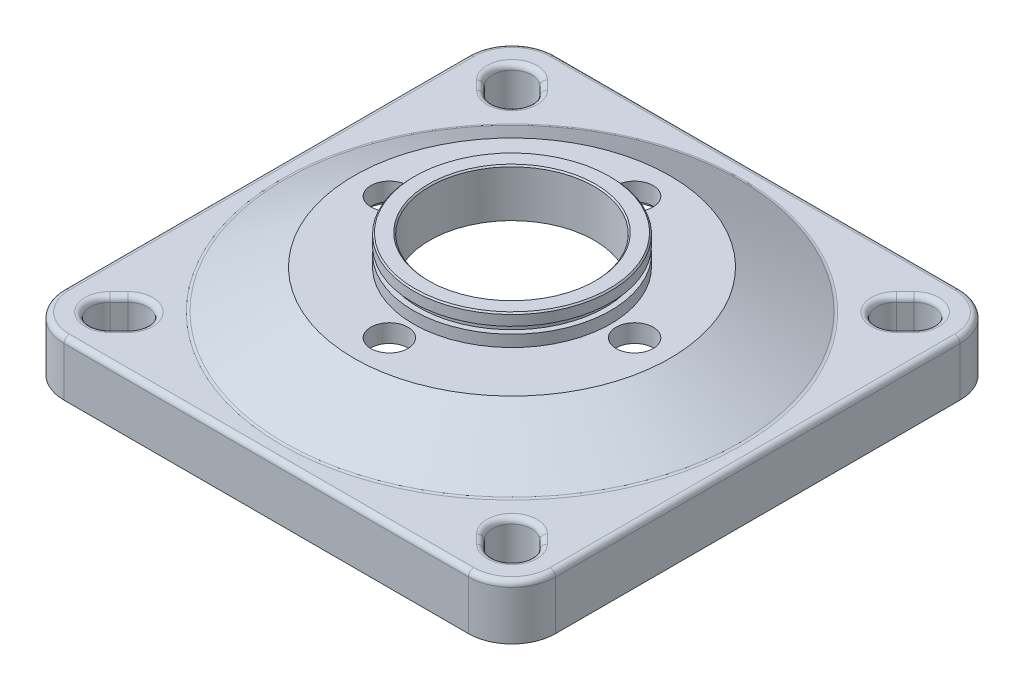
SolidWorks part; units mm, degrees
ref_plane "Front Plane" through (0, 0, 0) normal (0, 0, 1) x (1, 0, 0)
ref_plane "Top Plane" through (0, 0, 0) normal (0, 1, 0) x (1, 0, 0)
ref_plane "Right Plane" through (0, 0, 0) normal (1, 0, 0) x (0, 0, -1)
sketch "Sketch1" plane through (0, 0, 0) normal (0, 0, 1) x (1, 0, 0)
  line L0 (41.9647, 0) -> (-41.9647, 0) construction
  line L1 (-42, 0) -> (-42, 2.8529)
  line L2 (-42, 2.8529) -> (-29, 10)
  line L3 (-29, 10) -> (-18.1, 10)
  line L4 (-18.1, 10) -> (-18.1, 12.125)
  line L5 (-18.1, 12.125) -> (-17.1, 12.125)
  line L6 (-17.1, 12.125) -> (-17.1, 13.375)
  line L7 (-17.1, 13.375) -> (-18.1, 13.375)
  line L8 (-18.1, 13.375) -> (-18.1, 15.5)
  line L9 (-18.1, 15.5) -> (-15.1, 15.5)
  line L10 (-20.1376, 12.75) -> (-11.0446, 12.75) construction
  line L11 (0, 0) -> (0, 22.8552) construction
  line L12 (-15.1, 15.5) -> (-15.1, 7.5)
  line L13 (-15.1, 7.5) -> (-28.3581, 7.5)
  line L14 (-28.3581, 7.5) -> (-42, 0)
  point P4 (0, 0)
  dimension "D1" = 5.5
  dimension "D2" = 1.25
  dimension "D3" = 3
  dimension "D4" = 1
  dimension "D5" = 15.1
  dimension "D6" = 29
  dimension "D7" = 42
  dimension "D8" = 10
  dimension "D9" = 2.5
  dimension "D10" = 2.5
revolve "Revolve1" add sketch "Sketch1" angle 360 about L11
ref_plane "Plane1" through (0, 2.8529, 0) normal (0, 1, 0) x (1, 0, 0)
sketch "Sketch2" plane through (0, 2.8529, 0) normal (0, 1, 0) x (1, 0, 0)
  line L0 (36.0616, 36.0616) -> (32.7028, 32.7028)
  line L1 (37.1, -45.1) -> (-37.1, -45.1)
  line L2 (45.1, -37.1) -> (45.1, 37.1)
  line L3 (37.1, 45.1) -> (-37.1, 45.1)
  line L4 (-45.1, -37.1) -> (-45.1, 37.1)
  line L5 (45.1, -45.1) -> (-45.1, 45.1) construction
  line L6 (45.1, 45.1) -> (-45.1, -45.1) construction
  line L7 (36.0616, 36.0616) -> (39.4203, 39.4203)
  line L8 (34.3291, 39.4203) -> (32.7028, 37.794)
  line L9 (39.4203, 34.3291) -> (37.794, 32.7028)
  line L10 (34.3292, -39.4174) -> (32.7029, -37.791)
  line L11 (39.4204, -34.3262) -> (37.7941, -32.6999)
  line L12 (-39.4173, -34.3263) -> (-37.7909, -32.7)
  line L13 (-34.3261, -39.4175) -> (-32.6998, -37.7911)
  line L14 (-34.3262, 39.4202) -> (-32.6999, 37.7939)
  line L15 (-39.4174, 34.329) -> (-37.791, 32.7027)
  arc A0 (39.4203, 34.3291) -> (34.3291, 39.4203) centre (36.8747, 36.8747) ccw
  arc A1 (32.7028, 37.794) -> (37.794, 32.7028) centre (35.2484, 35.2484) ccw
  circle A2 centre (0, 0) radius 50.9987 construction
  arc A3 (45.1, -37.1) -> (37.1, -45.1) centre (37.1, -37.1) cw
  arc A4 (-37.1, -45.1) -> (-45.1, -37.1) centre (-37.1, -37.1) cw
  arc A5 (-45.1, 37.1) -> (-37.1, 45.1) centre (-37.1, 37.1) cw
  arc A6 (45.1, 37.1) -> (37.1, 45.1) centre (37.1, 37.1) ccw
  arc A7 (34.3292, -39.4174) -> (39.4204, -34.3262) centre (36.8748, -36.8718) ccw
  arc A8 (37.7941, -32.6999) -> (32.7029, -37.791) centre (35.2485, -35.2455) ccw
  arc A9 (-39.4173, -34.3263) -> (-34.3261, -39.4175) centre (-36.8717, -36.8719) ccw
  arc A10 (-32.6998, -37.7911) -> (-37.7909, -32.7) centre (-35.2454, -35.2456) ccw
  arc A11 (-34.3262, 39.4202) -> (-39.4174, 34.329) centre (-36.8718, 36.8746) ccw
  arc A12 (-37.791, 32.7027) -> (-32.6999, 37.7939) centre (-35.2455, 35.2483) ccw
  circle A13 centre (0, 0) radius 42 construction
  circle A14 centre (0, 0) radius 42
  point P0 (0, 0)
  point P50 (0.0015, 0.0014)
  dimension "D3" = 7.2
  dimension "D4" = 4.75
  dimension "D6" = 8
  dimension "D1" = 90.2
  dimension "D2" = 90.2
  dimension "D5" = 4.75
  dimension "D7" = 4
extrude "Boss-Extrude1" add sketch "Sketch2" against normal blind 10 contours L2 A6 L3 A5 L4 A4 L1 A3 A12 L15 A11 L14 A10 L13 A9 L12 A8 L11 A7 L10 A1 L8 A0 L9 region at (0, 2.8529, 43.8244)
sketch "Sketch3" plane through (0, -7.1471, 0) normal (0, -1, 0) x (1, 0, 0)
  line L0 (-40.8304, 31.2137) -> (-40.0576, 30.4409)
  line L1 (-30.4409, 40.0576) -> (-31.215, 40.8316)
  line L4 (31.2137, 40.8304) -> (30.4409, 40.0576)
  line L5 (40.0576, 30.4409) -> (40.8316, 31.215)
  line L6 (-45.1, 37.1) -> (-45.1, -37.1) construction
  line L7 (37.1, 45.1) -> (-37.1, 45.1) construction
  line L10 (37.1, 45.1) -> (-37.1, 45.1)
  line L11 (-45.1, 37.1) -> (-45.1, 2.9917)
  line L12 (41.6852, 30.8619) -> (41.6975, 18.8382)
  line L13 (30.8602, 41.6839) -> (18.8672, 41.6839)
  line L14 (-30.8619, 41.6852) -> (-18.8382, 41.6975)
  line L15 (40.8304, -31.2137) -> (40.0576, -30.4409)
  line L16 (-41.6839, 30.8602) -> (-41.6839, 18.8672)
  line L17 (30.4409, -40.0576) -> (31.215, -40.8316)
  line L18 (-45.1, -2.9917) -> (-45.1, -37.1)
  line L19 (30.8619, -41.6852) -> (18.8382, -41.6975)
  line L20 (41.6839, -30.8602) -> (41.6839, -18.8672)
  line L21 (-31.2137, -40.8304) -> (-30.4409, -40.0576)
  line L22 (-40.0576, -30.4409) -> (-40.8316, -31.215)
  line L23 (-41.6852, -30.8619) -> (-41.6975, -18.8382)
  line L24 (-30.8602, -41.6839) -> (-18.8672, -41.6839)
  arc A1 (-18.6297, 40.7428) -> (-18.8382, 41.6975) centre (-18.8377, 41.1975) ccw
  arc A2 (-40.0576, 30.4409) -> (-35.6149, 28.4591) centre (-35.2493, 35.2493) ccw
  arc A4 (-27.6512, 35.2484) -> (-28.4591, 35.6149) centre (-27.9598, 35.6418) cw
  arc A9 (-35.2484, 27.6512) -> (-40.7294, 18.659) centre (0, 0) ccw
  arc A10 (-28.4591, 35.6149) -> (-30.4409, 40.0576) centre (-35.2493, 35.2493) ccw
  arc A11 (-18.6297, 40.7428) -> (-27.6512, 35.2484) centre (0, 0) ccw
  arc A12 (-31.215, 40.8316) -> (-30.8619, 41.6852) centre (-30.8614, 41.1852) cw
  arc A13 (-41.6839, 18.8672) -> (-40.7294, 18.659) centre (-41.1839, 18.8672) ccw
  arc A14 (-35.2484, 27.6512) -> (-35.6149, 28.4591) centre (-35.6418, 27.9598) ccw
  arc A15 (-41.6839, 30.8602) -> (-40.8304, 31.2137) centre (-41.1839, 30.8602) cw
  arc A16 (40.7428, 18.6297) -> (41.6975, 18.8382) centre (41.1975, 18.8377) ccw
  arc A17 (30.4409, 40.0576) -> (28.4591, 35.6149) centre (35.2493, 35.2493) ccw
  arc A18 (35.2484, 27.6512) -> (35.6149, 28.4591) centre (35.6418, 27.9598) cw
  arc A19 (32.7037, 37.7949) -> (37.7949, 32.7037) centre (35.2493, 35.2493) ccw
  arc A21 (27.6512, 35.2484) -> (18.659, 40.7294) centre (0, 0) ccw
  arc A22 (35.6149, 28.4591) -> (40.0576, 30.4409) centre (35.2493, 35.2493) ccw
  arc A23 (40.7428, 18.6297) -> (35.2484, 27.6512) centre (0, 0) ccw
  arc A24 (40.8316, 31.215) -> (41.6852, 30.8619) centre (41.1852, 30.8614) cw
  arc A25 (18.8672, 41.6839) -> (18.659, 40.7294) centre (18.8672, 41.1839) ccw
  arc A26 (27.6512, 35.2484) -> (28.4591, 35.6149) centre (27.9598, 35.6418) ccw
  arc A27 (30.8602, 41.6839) -> (31.2137, 40.8304) centre (30.8602, 41.1839) cw
  arc A28 (18.6297, -40.7428) -> (18.8382, -41.6975) centre (18.8377, -41.1975) ccw
  arc A29 (40.0576, -30.4409) -> (35.6149, -28.4591) centre (35.2493, -35.2493) ccw
  arc A30 (27.6512, -35.2484) -> (28.4591, -35.6149) centre (27.9598, -35.6418) cw
  arc A33 (35.2484, -27.6512) -> (40.7294, -18.659) centre (0, 0) ccw
  arc A34 (28.4591, -35.6149) -> (30.4409, -40.0576) centre (35.2493, -35.2493) ccw
  arc A35 (18.6297, -40.7428) -> (27.6512, -35.2484) centre (0, 0) ccw
  arc A36 (31.215, -40.8316) -> (30.8619, -41.6852) centre (30.8614, -41.1852) cw
  arc A37 (41.6839, -18.8672) -> (40.7294, -18.659) centre (41.1839, -18.8672) ccw
  arc A38 (35.2484, -27.6512) -> (35.6149, -28.4591) centre (35.6418, -27.9598) ccw
  arc A39 (41.6839, -30.8602) -> (40.8304, -31.2137) centre (41.1839, -30.8602) cw
  arc A40 (-40.7428, -18.6297) -> (-41.6975, -18.8382) centre (-41.1975, -18.8377) ccw
  arc A41 (-30.4409, -40.0576) -> (-28.4591, -35.6149) centre (-35.2493, -35.2493) ccw
  arc A42 (-35.2484, -27.6512) -> (-35.6149, -28.4591) centre (-35.6418, -27.9598) cw
  arc A45 (-27.6512, -35.2484) -> (-18.659, -40.7294) centre (0, 0) ccw
  arc A46 (-35.6149, -28.4591) -> (-40.0576, -30.4409) centre (-35.2493, -35.2493) ccw
  arc A47 (-40.7428, -18.6297) -> (-35.2484, -27.6512) centre (0, 0) ccw
  arc A48 (-40.8316, -31.215) -> (-41.6852, -30.8619) centre (-41.1852, -30.8614) cw
  arc A49 (-18.8672, -41.6839) -> (-18.659, -40.7294) centre (-18.8672, -41.1839) ccw
  arc A50 (-27.6512, -35.2484) -> (-28.4591, -35.6149) centre (-27.9598, -35.6418) ccw
  arc A51 (-30.8602, -41.6839) -> (-31.2137, -40.8304) centre (-30.8602, -41.1839) cw
  point P12 (0, 0)
  point P14 (-16.3753, 41.7)
  point P21 (36.7, 41.7)
  point P22 (-36.7, 41.7)
  point P23 (-41.7, 36.7)
  point P24 (-41.7, -36.7)
  point P27 (44.8, 0)
  point P35 (40.1648, 12.2796)
  point P126 (0, 0)
  dimension "D1" = 0.5
  dimension "D3" = 4
extrude "Cut-Extrude1" cut sketch "Sketch3" against normal blind 8 contours A12 L1 A10 A4 A11 A1 L14 | A15 L16 A13 A9 A14 A2 L0 | A27 L13 A25 A21 A26 A17 L4 | A24 L5 A22 A18 A23 A16 L12 | A39 L20 A37 A33 A38 A29 L15 | A36 L17 A34 A30 A35 A28 L19 | A51 L24 A49 A45 A50 A41 L21 | A48 L22 A46 A42 A47 A40 L23 region at (-39.5477, -7.1471, 25.6034) region at (-25.5937, -7.1471, 39.5534) region at (25.6034, -7.1471, 39.5477) region at (39.5534, -7.1471, 25.5937) region at (39.5477, -7.1471, -25.6034) region at (25.5937, -7.1471, -39.5534) region at (-25.6034, -7.1471, -39.5477) region at (-39.5534, -7.1471, -25.5937)
sketch "Sketch4" plane through (0, 10, 0) normal (0, 1, 0) x (1, 0, 0)
  circle A0 centre (0, 0) radius 22.5 construction
  circle A1 centre (0, 22.5) radius 3.4
  circle A2 centre (22.5, 0) radius 3.4
  circle A3 centre (0, -22.5) radius 3.4
  circle A4 centre (-22.5, 0) radius 3.4
  point P14 (0, 0)
  dimension "D1" = 6.8
  dimension "D2" = 4
extrude "Cut-Extrude2" cut sketch "Sketch4" against normal blind 8
sketch "Sketch5" plane through (0, 7.5, 0) normal (0, -1, 0) x (1, 0, 0)
  line L0 (0, 0) -> (-35.2455, -35.2483) construction
ref_plane "Plane2" through (0, 0, 0) normal (-0.7071, 0, 0.7071) x (-0.7071, 0, -0.7071)
sketch "Sketch6" plane through (0, 0, 0) normal (-0.7071, 0, 0.7071) x (-0.7071, 0, -0.7071)
  line L0 (18.6181, -7.5) -> (40.5126, -0.8177)
  line L1 (0, -7.5) -> (49.8466, -7.5) construction
  line L2 (28.3581, -7.5) -> (42, 0) construction
  line L3 (40.5126, -0.8177) -> (28.3581, -7.5)
  line L4 (28.3581, -7.5) -> (18.6181, -7.5)
extrude "Boss-Extrude2" add sketch "Sketch6" along normal mid plane 3.8
fillet "Fillet1" radius 2 2 edges at (-22.2131, 4.1742, -19.5278) (-19.526, 4.1742, -22.2147)
pattern_circular "CirPattern1" count 4 over 360 about axis through (0, 7.5, 0) along (0, -1, 0) of "Boss-Extrude2", "Fillet1"
sketch "Sketch7" plane through (0, 7.5, 0) normal (0, -1, 0) x (1, 0, 0)
  line L0 (22.5, 6) -> (29.1147, 6)
  line L1 (22.5, -6) -> (29.1147, -6)
  line L2 (-6, 22.5) -> (-6, 29.1147)
  line L3 (-6, 29.1147) -> (6, 29.1147)
  line L4 (6, 22.5) -> (6, 29.1147)
  line L5 (29.1147, 6) -> (29.1147, -6)
  line L6 (6, -22.5) -> (6, -29.1147)
  line L7 (-6, -22.5) -> (-6, -29.1147)
  line L8 (6, -29.1147) -> (-6, -29.1147)
  line L9 (-22.5, -6) -> (-29.1147, -6)
  line L10 (-22.5, 6) -> (-29.1147, 6)
  line L11 (-29.1147, -6) -> (-29.1147, 6)
  arc A0 (3.5324, 17.65) -> (6, 22.5) centre (0, 22.5) ccw
  circle A1 centre (0, 0) radius 7.6
  arc A2 (3.5324, -17.65) -> (17.65, -3.5324) centre (0, 0) ccw
  arc A3 (17.65, -3.5324) -> (22.5, -6) centre (22.5, 0) ccw
  arc A4 (-3.5324, -17.65) -> (-6, -22.5) centre (0, -22.5) ccw
  arc A5 (-17.65, 3.5324) -> (-22.5, 6) centre (-22.5, 0) ccw
  arc A6 (17.65, 3.5324) -> (3.5324, 17.65) centre (0, 0) ccw
  arc A7 (-3.5324, 17.65) -> (-17.65, 3.5324) centre (0, 0) ccw
  arc A8 (-17.65, -3.5324) -> (-3.5324, -17.65) centre (0, 0) ccw
  arc A9 (-6, 22.5) -> (-3.5324, 17.65) centre (0, 22.5) ccw
  arc A10 (22.5, 6) -> (17.65, 3.5324) centre (22.5, 0) ccw
  arc A11 (6, -22.5) -> (3.5324, -17.65) centre (0, -22.5) ccw
  arc A12 (-22.5, -6) -> (-17.65, -3.5324) centre (-22.5, 0) ccw
  point P16 (0, 0)
  point P36 (0, 0)
  dimension "D2" = 12
  dimension "D3" = 36
  dimension "D1" = 4
  dimension "D4" = 4
extrude "Boss-Extrude3" add sketch "Sketch7" along normal blind 0.8
sketch "Sketch9" plane through (0, 7.5, 0) normal (0, 1, 0) x (1, 0, 0)
  circle A0 centre (-22.5, 0) radius 3.4 construction
  circle A1 centre (0, 0) radius 15.1
  circle A2 centre (0, 0) radius 15.1
  circle A3 centre (0, 22.5) radius 3.4 construction
  circle A4 centre (22.5, 0) radius 3.4 construction
  circle A5 centre (0, -22.5) radius 3.4 construction
  circle A6 centre (-22.5, 0) radius 3.4
  circle A7 centre (0, 22.5) radius 3.4
  circle A8 centre (22.5, 0) radius 3.4
  circle A9 centre (0, -22.5) radius 3.4
  dimension "D1" = 0
extrude "Cut-Extrude3" cut sketch "Sketch9" against normal blind 0.8
fillet "Fillet3" radius 1 25 edges at (42.7569, 2.8529, 42.7569) (0, 2.8529, 45.1) (-42.7569, 2.8529, 42.7569) (-45.1, 2.8529, 0) (-42.7569, 2.8529, -42.7569) (0, 2.8529, -45.1) (42.7569, 2.8529, -42.7569) (45.1, 2.8529, 0) (38.6071, 2.8529, -33.516) (39.4203, 2.8529, -39.4203) (33.516, 2.8529, -38.6071) (32.7028, 2.8529, -32.7028) (33.5161, 2.8529, 38.6042) (39.4204, 2.8529, 39.4174) (38.6072, 2.8529, 33.5131) (32.7029, 2.8529, 32.6999) (-38.6041, 2.8529, 33.5132) (-39.4173, 2.8529, 39.4175) (-33.5129, 2.8529, 38.6043) (-32.6998, 2.8529, 32.7) (-33.5131, 2.8529, -38.607) (-39.4174, 2.8529, -39.4202) (-38.6042, 2.8529, -33.5159) (-32.6999, 2.8529, -32.7027) (0, 2.8529, -42)
chamfer "Chamfer1" distance 0.25 angle 45 2 edges at (0, 15.5, -15.1) (0, 15.5, -18.1)
